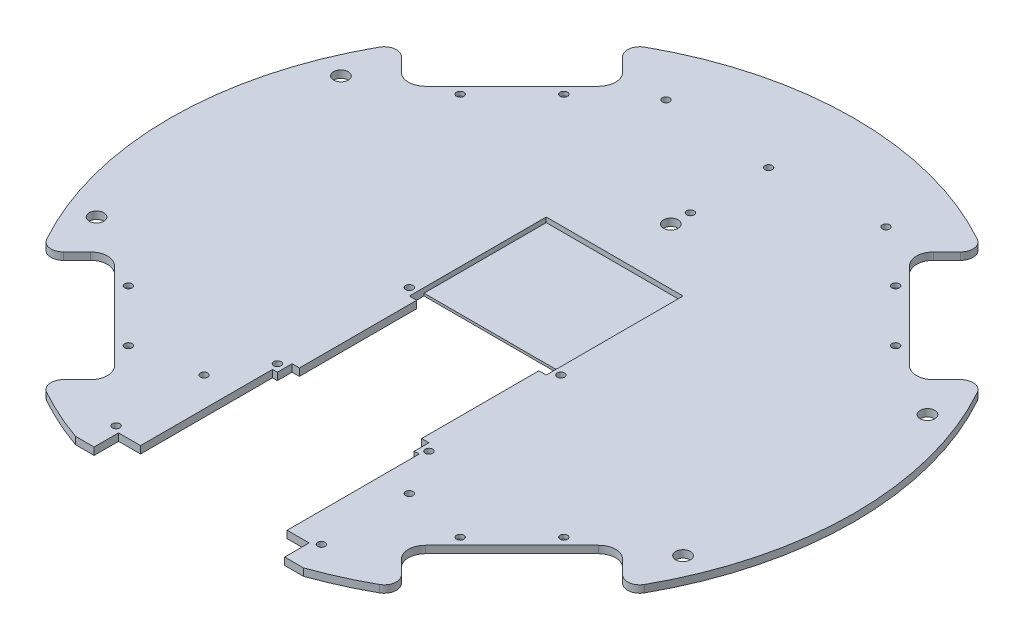
SolidWorks part; units mm, degrees
material "1060 Alloy"
ref_plane "Front Plane" through (0, 0, 0) normal (0, 0, 1) x (1, 0, 0)
ref_plane "Top Plane" through (0, 0, 0) normal (0, 1, 0) x (1, 0, 0)
ref_plane "Right Plane" through (0, 0, 0) normal (1, 0, 0) x (0, 0, -1)
sketch "Sketch1" plane through (0, 0, 0) normal (0, 1, 0) x (1, 0, 0)
  circle A0 centre (0, 0) radius 140
  dimension "D1" = 280
extrude "Boss-Extrude1" add sketch "Sketch1" along normal blind 3
sketch "Sketch7" plane through (0, 3, 0) normal (0, 1, 0) x (1, 0, 0)
  line L0 (-99.0303, -63.6043) -> (-63.6043, -99.0303)
  line L1 (-108.8591, -63.6043) -> (-121.6224, -76.3675)
  line L2 (-63.6043, -108.8591) -> (-76.3675, -121.6224)
  line L3 (-121.6224, -76.3675) -> (-76.3675, -121.6224)
  line L4 (0, 0) -> (-98.9949, -98.9949) construction
  line L7 (0, 0) -> (0, 130) construction
  circle A0 centre (0, 0) radius 140 construction
  arc A1 (-108.8591, -63.6043) -> (-99.0303, -63.6043) centre (-103.9447, -68.5186) cw
  arc A2 (-63.6043, -99.0303) -> (-63.6043, -108.8591) centre (-68.5186, -103.9447) cw
  dimension "D4" = 6.95
  dimension "D1" = 115
  dimension "D2" = 64
  dimension "D3" = 135
extrude "Cut-Extrude4" cut sketch "Sketch7" against normal up to next
sketch "Sketch9" plane through (0, 3, 0) normal (0, 1, 0) x (1, 0, 0)
  line L1 (-63.6043, -99.0303) -> (-99.0303, -63.6043) construction
  line L4 (-108.8591, -63.6043) -> (-119.0017, -73.7469) construction
  circle A0 centre (-89.0955, -67.8823) radius 1.5
  circle A1 centre (-67.8823, -89.0955) radius 1.5
  dimension "D4" = 3
  dimension "D1" = 4
  dimension "D2" = 30
  dimension "D3" = 17
  dimension "D5" = 4
extrude "Cut-Extrude6" cut sketch "Sketch9" against normal up to next
fillet "Fillet1" radius 5 2 edges at (-73.7469, 1.5, 119.0017) (-119.0017, 1.5, 73.7469)
pattern_circular "CirPattern1" count 4 over 360 about axis through (0, 3, 0) along (0, 1, 0) of "Cut-Extrude4", "Fillet1", "Cut-Extrude6"
sketch "Sketch2" plane through (0, 3, 0) normal (0, 1, 0) x (1, 0, 0)
  line L0 (-46.6476, -132) -> (-39, -132)
  line L1 (-30, -122) -> (-30, -68)
  line L2 (-28, -8) -> (28, -8)
  line L3 (30, -68) -> (30, -122)
  line L4 (39, -132) -> (46.6476, -132)
  line L5 (46.6476, -132) -> (46.6476, -140)
  line L6 (46.6476, -140) -> (-46.6476, -140)
  line L7 (-46.6476, -140) -> (-46.6476, -132)
  line L8 (-28, -62) -> (-28, -68)
  line L9 (-28, -68) -> (-30, -68)
  line L10 (28, -62) -> (28, -68)
  line L11 (28, -68) -> (30, -68)
  line L12 (-28, -62) -> (-25, -62)
  line L13 (-25, -62) -> (-25, -14)
  line L14 (-25, -14) -> (-28, -14)
  line L15 (-28, -14) -> (-28, -8)
  line L16 (28, -8) -> (28, -14)
  line L17 (28, -14) -> (25, -14)
  line L18 (25, -14) -> (25, -62)
  line L19 (25, -62) -> (28, -62)
  line L20 (-39, -132) -> (-39, -122)
  line L21 (-39, -122) -> (-30, -122)
  line L22 (39, -132) -> (39, -122)
  line L23 (39, -122) -> (30, -122)
  circle A0 centre (0, 0) radius 140 construction
  dimension "D8" = 3
  dimension "D5" = 60
  dimension "D6" = 56
  dimension "D1" = 8
  dimension "D2" = 124
  dimension "D3" = 60
  dimension "D4" = 16.6476
  dimension "D7" = 6
  dimension "D9" = 78
  dimension "D10" = 10
extrude "Cut-Extrude1" cut sketch "Sketch2" against normal up to next
fillet "Fillet3" radius 1.5 8 edges at (67.8823, 0, 90.5955) (89.0955, 0, 69.3823) (89.0955, 0, -66.3823) (67.8823, 0, -87.5955) (-67.8823, 0, -87.5955) (-89.0955, 0, -66.3823) (-67.8823, 0, 90.5955) (-89.0955, 0, 69.3823)
sketch "Sketch10" plane through (0, 3, 0) normal (0, 1, 0) x (1, 0, 0)
  circle A0 centre (-31, -65) radius 1.5
  circle A1 centre (31, -65) radius 1.5
  circle A2 centre (-31, -11) radius 1.5
  circle A3 centre (31, -11) radius 1.5
  dimension "D3" = 3
  dimension "D1" = 31
  dimension "D2" = 62
  dimension "D4" = 65
  dimension "D5" = 54
extrude "Cut-Extrude7" cut sketch "Sketch10" against normal up to next
sketch "Sketch13" plane through (0, 3, 0) normal (0, 1, 0) x (1, 0, 0)
  line L1 (-39, -132) -> (-46.6476, -132) construction
  circle A0 centre (-42, -84) radius 1.5
  circle A1 centre (-42, -120) radius 1.5
  circle A2 centre (42, -120) radius 1.5
  circle A3 centre (42, -84) radius 1.5
  dimension "D1" = 3
  dimension "D2" = 12
  dimension "D3" = 36
  dimension "D4" = 42
  dimension "D5" = 42
extrude "Cut-Extrude9" cut sketch "Sketch13" against normal up to next
sketch "Sketch16" plane through (0, 3, 0) normal (0, 1, 0) x (1, 0, 0)
  circle A0 centre (0, 73) radius 1.5
  circle A1 centre (-45, 108) radius 1.5
  circle A2 centre (45, 108) radius 1.5
  circle A3 centre (0, 105) radius 1.5
  circle A4 centre (0, 65) radius 3
  dimension "D2" = 3
  dimension "D5" = 6
  dimension "D1" = 73
  dimension "D3" = 108
  dimension "D4" = 90
  dimension "D6" = 32
  dimension "D7" = 65
extrude "Cut-Extrude12" cut sketch "Sketch16" against normal up to next
sketch "Sketch17" plane through (0, 3, 0) normal (0, 1, 0) x (1, 0, 0)
  circle A0 centre (-120, 50) radius 3
  circle A1 centre (-120, -50) radius 3
  circle A2 centre (120, 50) radius 3
  circle A3 centre (120, -50) radius 3
  dimension "D1" = 6
  dimension "D2" = 50
  dimension "D3" = 50
  dimension "D4" = 120
  dimension "D5" = 120
extrude "Cut-Extrude13" cut sketch "Sketch17" against normal up to next
sketch "Sketch18" plane through (0, 3, 0) normal (0, 1, 0) x (1, 0, 0)
  line L0 (-28, -8) -> (-28, -14) construction
  line L1 (-28, -8) -> (28, -8)
  line L2 (-28, -8) -> (-28, 42)
  line L3 (-28, 42) -> (28, 42)
  line L4 (28, -8) -> (28, 42)
  line L5 (28, -8) -> (-28, -8) construction
  line L6 (28, -8) -> (-28, -8) construction
  dimension "D1" = 50
extrude "Cut-Extrude14" cut sketch "Sketch18" against normal blind 2
